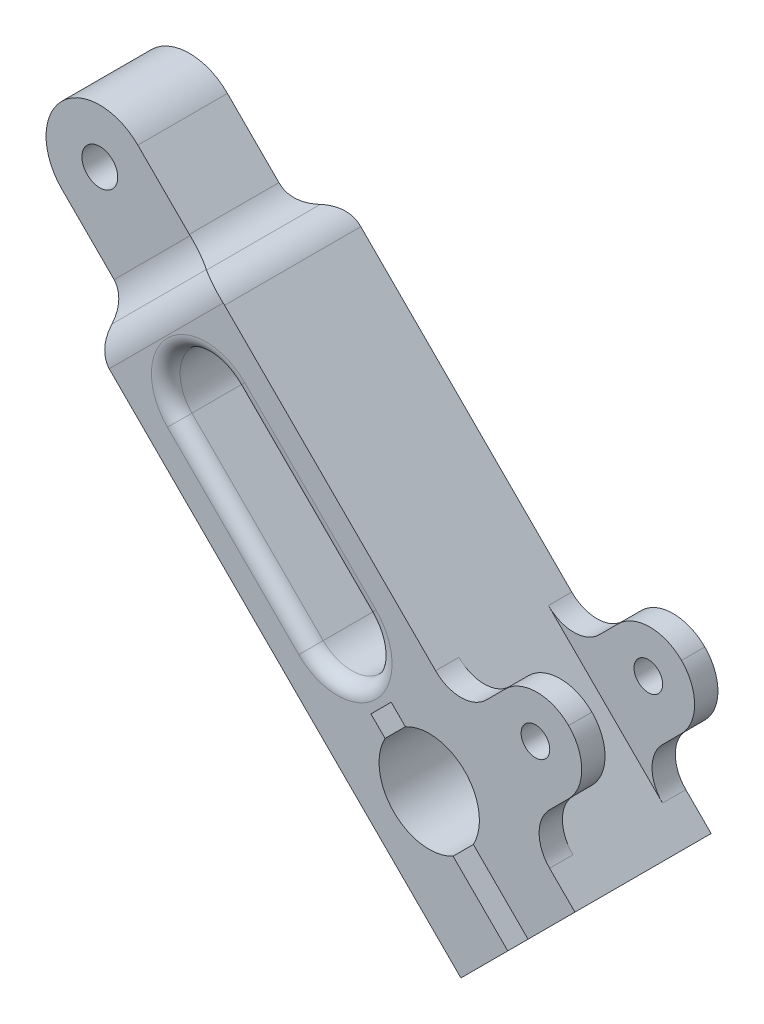
SolidWorks part; units mm, degrees
ref_plane "Front Plane" through (0, 0, 0) normal (0, 0, 1) x (1, 0, 0)
ref_plane "Top Plane" through (0, 0, 0) normal (0, 1, 0) x (1, 0, 0)
ref_plane "Right Plane" through (0, 0, 0) normal (1, 0, 0) x (0, 0, -1)
sketch "Sketch2" plane through (0, 0, 0) normal (0, 0, 1) x (1, 0, 0)
  line L0 (0, 0) -> (-234.0257, 0) construction
  line L1 (0, 0) -> (132.15, 132.15) construction
  line L2 (0, 0) -> (130.2279, -130.2279) construction
  line L3 (-10.6066, -10.6066) -> (10.6066, 10.6066) construction
  line L4 (-10.6066, -10.6066) -> (21.2132, -42.4264) construction
  line L5 (21.2132, -42.4264) -> (42.4264, -21.2132) construction
  line L6 (42.4264, -21.2132) -> (10.6066, 10.6066) construction
  line L7 (0, -21.2132) -> (21.2132, 0)
  line L9 (21.2132, 0) -> (53.033, -31.8198)
  line L10 (0, -21.2132) -> (31.8198, -53.033)
  line L11 (31.8198, -53.033) -> (26.5165, -58.3363)
  line L12 (114.318, -146.1378) -> (26.5165, -58.3363)
  line L13 (53.033, -31.8198) -> (58.3363, -26.5165)
  line L14 (128.4601, -96.6403) -> (58.3363, -26.5165)
  line L15 (146.1378, -114.318) -> (167.351, -93.1047)
  line L16 (167.351, -93.1047) -> (149.6733, -75.4271)
  line L17 (149.6733, -75.4271) -> (128.4601, -96.6403)
  line L18 (158.5121, -84.2659) -> (119.6213, -119.6213) construction
  line L19 (146.1378, -114.318) -> (160.2799, -128.4601)
  line L20 (114.318, -146.1378) -> (128.4601, -160.2799)
  line L21 (160.2799, -128.4601) -> (147.1984, -141.5416)
  line L22 (109.0147, -103.3578) -> (112.9628, -107.306)
  line L23 (103.3578, -109.0147) -> (109.0147, -103.3578)
  line L24 (103.3578, -109.0147) -> (107.306, -112.9628)
  line L25 (131.9365, -126.2797) -> (147.1984, -141.5416)
  line L26 (126.2797, -131.9365) -> (141.5416, -147.1984)
  line L27 (141.5416, -147.1984) -> (128.4601, -160.2799)
  line L28 (31.8198, -53.033) -> (53.033, -31.8198)
  line L29 (128.4601, -96.6403) -> (146.1378, -114.318)
  circle A0 centre (21.2132, -21.2132) radius 5
  circle A1 centre (149.2524, -92.6839) radius 4
  arc A2 (107.306, -112.9628) -> (126.2797, -131.9365) centre (119.6213, -119.6213) ccw
  arc A3 (131.9365, -126.2797) -> (112.9628, -107.306) centre (119.6213, -119.6213) ccw
  point P8 (0, 0)
  point P15 (10.6066, -10.6066)
  point P18 (130.2279, -130.2279)
  point P35 (111.5259, -126.9806)
  point P40 (106.1862, -106.1862)
  dimension "D4" = 10
  dimension "D5" = 15
  dimension "D12" = 8
  dimension "D13" = 12.5
  dimension "D14" = 28
  dimension "D1" = 184.17
  dimension "D2" = 30
  dimension "D3" = 45
  dimension "D6" = 15
  dimension "D7" = 30
  dimension "D8" = 45
  dimension "D9" = 45
  dimension "D10" = 30
  dimension "D11" = 25
  dimension "D15" = 20
  dimension "D17" = 19
extrude "Boss-Extrude1" add sketch "Sketch2" along normal blind 38 contours A3 L25 L21 L19 L29 L14 L13 L28 L11 L12 L20 L27 L26 A2 L24 L23 L22 region at (89.1363, -89.1363, 0)
extrude "Boss-Extrude2" add sketch "Sketch2<3>" along normal blind 6.5 contours L17 L29 L15 L16 A1 region at (139.4556, -86.4226, 0)
sketch "Sketch2<3>" plane through (0, 0, 0) normal (0, 0, 1) x (1, 0, 0) same geometry as "Sketch2"
fillet "Fillet1" radius 12.5 2 edges at (167.351, -93.1047, 3.25) (149.6733, -75.4271, 3.25)
ref_plane "Plane1" through (0, 0, 19) normal (0, 0, -1) x (-1, 0, 0)
mirror "Mirror1" about plane through (0, 0, 19) normal (0, 0, -1) of "Boss-Extrude2", "Fillet1"
sketch "Sketch3" plane through (42.4264, -42.4264, 0) normal (-0.7071, 0.7071, 0) x (0, 0, 1)
  line L0 (19, 71.4684) -> (19, -71.4684) construction
  line L1 (6.5, 15) -> (31.5, 15)
  line L2 (6.5, 15) -> (6.5, -15)
  line L3 (6.5, -15) -> (31.5, -15)
  line L4 (31.5, 15) -> (31.5, -15)
  line L5 (6.5, 15) -> (31.5, -15) construction
  line L6 (6.5, -15) -> (31.5, 15) construction
  point P0 (19, 0)
  dimension "D1" = 30
  dimension "D2" = 25
extrude "Boss-Extrude3" add sketch "Sketch3" along normal blind 45
sketch "Sketch4" plane through (0, 0, 31.5) normal (0, 0, 1) x (1, 0, 0)
  line L0 (10.6066, -10.6066) -> (31.8198, -31.8198) construction
  line L1 (0, -21.2132) -> (21.2132, 0) construction
  circle A0 centre (21.2132, -21.2132) radius 5
  dimension "D1" = 10
  dimension "D2" = 15
extrude "Cut-Extrude1" cut sketch "Sketch4" against normal through all
fillet "Fillet2" radius 15 2 edges at (21.2132, 0, 19) (0, -21.2132, 19)
sketch "Sketch5" plane through (144.37, -144.37, 0) normal (0.7071, -0.7071, 0) x (0, 0, -1)
  line L0 (-38, -13.25) -> (0, -13.25) construction
  line L1 (-38, -4) -> (-38, -22.5) construction
  line L2 (0, -4) -> (0, -22.5) construction
  circle A0 centre (-27, -13.25) radius 4
  circle A1 centre (-13, -13.25) radius 4
  dimension "D1" = 8
  dimension "D2" = 8
  dimension "D3" = 14
  dimension "D4" = 11
fillet "Fillet3" radius 10 8 edges at (42.4264, -42.4264, 31.5) (31.8198, -53.033, 19) (53.033, -31.8198, 19) (42.4264, -42.4264, 6.5) (128.4601, -96.6403, 34.75) (128.4601, -96.6403, 3.25) (146.1378, -114.318, 34.75) (146.1378, -114.318, 3.25)
fillet "Fillet4" radius 10 4 edges at (42.4264, -42.4264, 0) (26.5165, -58.3363, 19) (42.4264, -42.4264, 38) (58.3363, -26.5165, 19)
sketch "Sketch6" plane through (0, 0, 0) normal (0, 0, -1) x (-1, 0, 0)
  line L0 (-46.2369, -46.2369) -> (-106.1862, -106.1862) construction
  line L1 (-30.3374, -62.1364) -> (-62.1364, -30.3374) construction
  line L2 (-103.3578, -109.0147) -> (-109.0147, -103.3578) construction
  line L3 (-57.366, -57.366) -> (-93.9989, -93.9989) construction
  line L4 (-49.4111, -65.321) -> (-86.044, -101.9539)
  line L5 (-65.321, -49.4111) -> (-101.9539, -86.044)
  line L6 (-46.2369, -46.2369) -> (-7.1246, -7.4244) construction
  line L7 (-41.0197, -41.0197) -> (-31.4603, -31.5736) construction
  line L8 (-54.1799, -27.8596) -> (-27.8596, -54.1799) construction
  line L9 (-45.2948, -36.6935) -> (-35.7353, -27.2473)
  line L10 (-36.7447, -45.346) -> (-27.1853, -35.8999)
  arc A0 (-49.4111, -65.321) -> (-65.321, -49.4111) centre (-57.366, -57.366) ccw
  arc A1 (-101.9539, -86.044) -> (-86.044, -101.9539) centre (-93.9989, -93.9989) ccw
  arc A2 (-45.2948, -36.6935) -> (-36.7447, -45.346) centre (-41.0197, -41.0197) ccw
  arc A3 (-27.1853, -35.8999) -> (-35.7353, -27.2473) centre (-31.4603, -31.5736) ccw
  point P8 (-75.6825, -75.6825)
  point P18 (-36.24, -36.2967)
  dimension "D1" = 11.25
extrude "Cut-Extrude3" cut sketch "Sketch6" against normal through all contours L5 A1 L4 A0
fillet "Fillet5" radius 4 8 edges at (49.4111, -49.4111, 0) (83.6374, -67.7275, 0) (101.9539, -101.9539, 0) (101.9539, -101.9539, 38) (83.6374, -67.7275, 38) (49.4111, -49.4111, 38) (67.7275, -83.6374, 0) (67.7275, -83.6374, 38)
sketch "Sketch8" plane through (-15.9099, -15.9099, 0) normal (-0.7071, -0.7071, 0) x (0, 0, 1)
  circle A0 centre (25.5207, -191.8383) radius 4.1672 construction
  circle A1 centre (25.5207, -151.8383) radius 4.1672 construction
  circle A2 centre (25.5207, -191.8383) radius 4.1672
  circle A3 centre (25.5207, -151.8383) radius 4.1672
extrude "Cut-Extrude4" cut sketch "Sketch8" against normal blind 10
